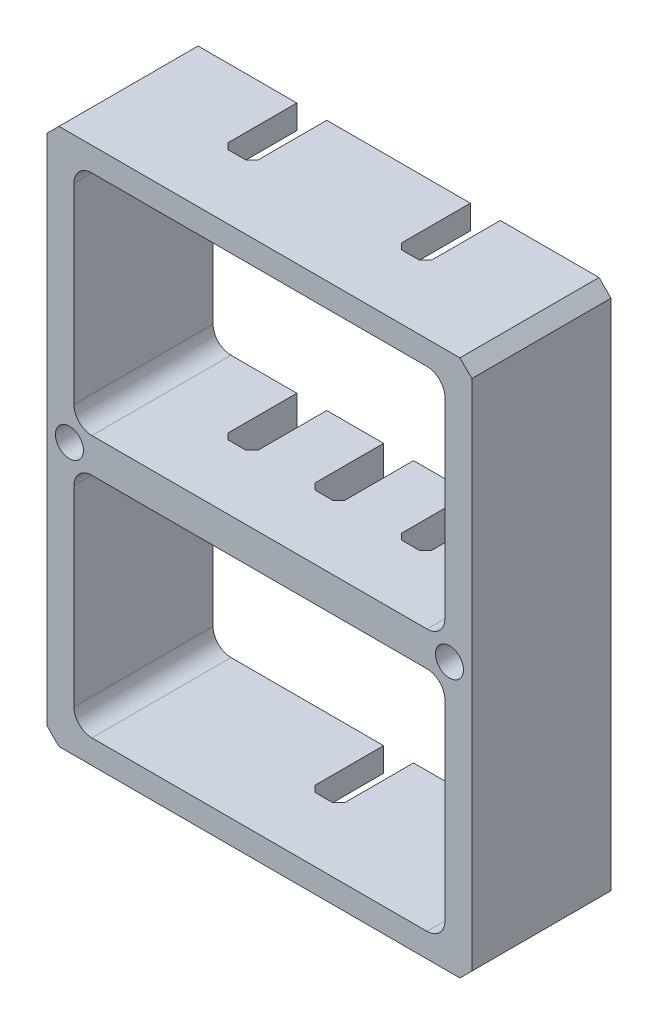
SolidWorks part; units mm, degrees
ref_plane "Front Plane" through (0, 0, 0) normal (0, 0, 1) x (1, 0, 0)
ref_plane "Top Plane" through (0, 0, 0) normal (0, 1, 0) x (1, 0, 0)
ref_plane "Right Plane" through (0, 0, 0) normal (1, 0, 0) x (0, 0, -1)
sketch "Sketch1" plane through (0, 0, 0) normal (0, 0, 1) x (1, 0, 0)
  line L4 (30.226, -70.2945) -> (30.226, -77.9145) construction
  line L5 (15.494, -69.7865) -> (30.226, -69.7865) construction
  line L6 (15.494, -69.7865) -> (15.494, -78.4225) construction
  line L7 (15.494, -78.4225) -> (30.226, -78.4225) construction
  line L12 (13.843, -79.9465) -> (31.877, -79.9465)
  line L13 (31.877, -79.9465) -> (31.877, -57.15)
  line L14 (31.877, -57.15) -> (13.843, -57.15)
  line L15 (13.843, -57.15) -> (13.843, -79.9465)
  line L16 (30.226, -69.7865) -> (30.226, -78.4225) construction
  line L17 (22.86, -78.4225) -> (22.86, -69.7865) construction
  line L18 (15.494, -74.1045) -> (30.226, -74.1045) construction
  line L19 (16.002, -69.7865) -> (29.718, -69.7865) construction
  line L20 (15.494, -77.9145) -> (15.494, -70.2945) construction
  line L21 (29.718, -78.4225) -> (16.002, -78.4225) construction
  line L22 (14.986, -69.2785) -> (30.734, -69.2785)
  line L23 (30.734, -69.2785) -> (30.734, -78.9305)
  line L24 (14.986, -78.9305) -> (30.734, -78.9305)
  line L25 (14.986, -69.2785) -> (14.986, -78.9305)
  line L26 (13.843, -68.5482) -> (31.877, -68.5482) construction
  line L27 (14.986, -67.818) -> (14.986, -58.166)
  line L28 (14.986, -58.166) -> (30.734, -58.166)
  line L29 (30.734, -67.818) -> (30.734, -58.166)
  line L30 (14.986, -67.818) -> (30.734, -67.818)
  point P208 (22.86, -74.1045)
  dimension "D2" = 0.508
  dimension "D3" = 22.7965
  dimension "D1" = 18.034
extrude "Boss-Extrude1" add sketch "Sketch1" along normal offset from surface (5.9055 mm away) 1.5875 contours L14 L15 L12 L13 L30 L27 L28 L29 L25 L22 L23 L24 region at (22.86, -68.5482, 0)
sketch "Sketch2" plane through (0, 0, 0) normal (0, 0, -1) x (-1, 0, 0)
  line L0 (-18.796, -57.404) -> (-19.558, -57.404) construction
  line L3 (-26.162, -57.404) -> (-26.924, -57.404) construction
  line L5 (-23.241, -68.58) -> (-22.479, -68.58) construction
  line L8 (-18.796, -68.5165) -> (-19.558, -68.5165) construction
  line L9 (-26.162, -68.5165) -> (-26.924, -68.5165) construction
  line L10 (-23.241, -79.6925) -> (-22.479, -79.6925) construction
  line L11 (-22.86, -78.9305) -> (-22.86, -79.9465)
  line L12 (-30.734, -78.9305) -> (-14.986, -78.9305) construction
  line L13 (-31.877, -79.9465) -> (-13.843, -79.9465) construction
  line L14 (-19.177, -57.15) -> (-19.177, -58.166)
  line L15 (-13.843, -57.15) -> (-31.877, -57.15) construction
  line L16 (-30.734, -58.166) -> (-14.986, -58.166) construction
  line L17 (-26.543, -57.15) -> (-26.543, -58.166)
  line L18 (-22.86, -69.2785) -> (-22.86, -67.818)
  line L19 (-30.734, -69.2785) -> (-14.986, -69.2785) construction
  line L20 (-30.734, -67.818) -> (-14.986, -67.818) construction
  line L21 (-19.177, -69.2785) -> (-19.177, -67.818)
  line L22 (-26.543, -69.2785) -> (-26.543, -67.818)
  point P0 (-19.177, -57.404)
  point P1 (-26.543, -57.404)
  point P4 (-22.86, -68.58)
  point P7 (-19.177, -68.5165)
  point P10 (-26.543, -68.5165)
  point P13 (-22.86, -79.6925)
extrude "Cut-Extrude-Thin2" cut sketch "Sketch2" against normal blind 3.175 thin contours L14 | L17 | L21 | L18 | L22 | L11 thin type mid plane wall 1.27
chamfer "Chamfer1" distance 0.254 angle 45 12 edges at (23.495, -79.4385, 3.175) (22.225, -79.4385, 3.175) (27.178, -68.5482, 3.175) (25.908, -68.5482, 3.175) (22.225, -68.5482, 3.175) (23.495, -68.5482, 3.175) (19.812, -68.5482, 3.175) (18.542, -68.5482, 3.175) (18.542, -57.658, 3.175) (19.812, -57.658, 3.175) (25.908, -57.658, 3.175) (27.178, -57.658, 3.175)
chamfer "Chamfer2" distance 0.508 angle 45 4 edges at (31.877, -57.15, 2.9528) (13.843, -57.15, 2.9528) (13.843, -79.9465, 2.9528) (31.877, -79.9465, 2.9528)
fillet "Fillet1" radius 0.762 8 edges at (14.986, -78.9305, 2.9528) (30.734, -78.9305, 2.9528) (30.734, -69.2785, 2.9528) (14.986, -69.2785, 2.9528) (14.986, -67.818, 2.9528) (30.734, -67.818, 2.9528) (14.986, -58.166, 2.9528) (30.734, -58.166, 2.9528)
hole_wizard "#0-80 Tapped Hole1" positions "Sketch4" profile "Sketch3" tap size "#0-80" standard "ANSI Inch" end condition through all
sketch "Sketch4" plane through (0, 0, 0) normal (0, 0, -1) x (-1, 0, 0)
  line L0 (-15.748, -69.2785) -> (-15.748, -67.818) construction
  line L2 (-15.748, -68.5482) -> (-13.843, -68.5482) construction
  line L3 (-13.843, -57.658) -> (-13.843, -79.4385) construction
  line L5 (-22.86, -57.15) -> (-22.86, -79.9465) construction
  line L6 (-25.908, -57.15) -> (-19.812, -57.15) construction
  line L7 (-22.479, -79.9465) -> (-23.241, -79.9465) construction
  point P12 (-14.7955, -68.5482)
  point P25 (-30.9245, -68.5482)
sketch "Sketch3" plane through (30.9245, -68.5482, 0) normal (1, 0, 0) x (0, 1, 0)
  line L0 (0, 0) -> (0, 5.9055)
  line L1 (0, 5.9055) -> (0.5956, 5.9055)
  line L2 (0.5956, 5.9055) -> (0.5956, 0)
  line L5 (0.5956, 0) -> (0, 0)
  line L11 (0, -6.35) -> (0, 107.95) construction
  dimension "Thru Tap Drill Dia." = 1.1913
  dimension "Thru Tap Drill Depth" = 5.9055
cosmetic thread "Hole Thread1" parameters "D2"=1.524
cosmetic thread "Hole Thread2" parameters "D2"=1.524
